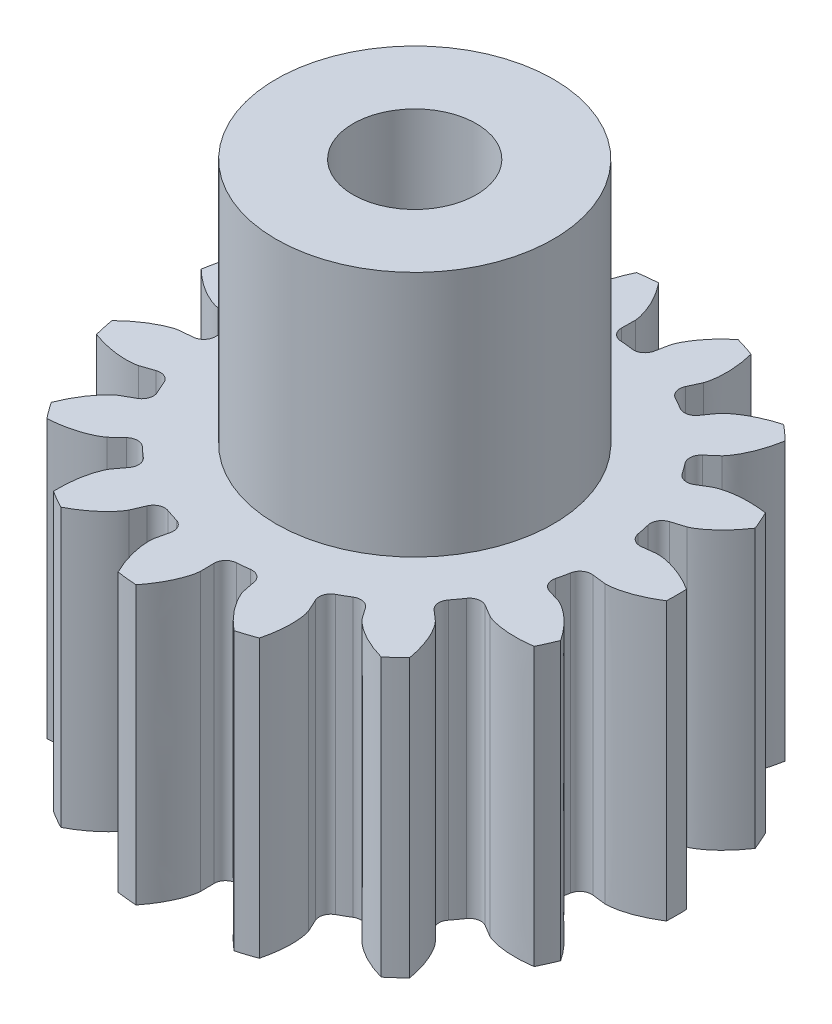
SolidWorks part; units mm, degrees
ref_plane "Front Plane" through (0, 0, 0) normal (0, 0, 1) x (1, 0, 0)
ref_plane "Top Plane" through (0, 0, 0) normal (0, 1, 0) x (1, 0, 0)
ref_plane "Right Plane" through (0, 0, 0) normal (1, 0, 0) x (0, 0, -1)
sketch "Sketch1" plane through (0, 0, 9) normal (0, -1, 0) x (1, 0, 0)
  line L0 (6.5671, -9.7894) -> (7.0134, -9.8423)
  line L1 (7.0134, -8.1577) -> (6.5671, -8.2106)
  line L2 (6.3204, -7.05) -> (6.7496, -6.9168)
  line L3 (6.0645, -5.378) -> (5.6783, -5.6078)
  line L4 (4.9809, -4.6479) -> (5.3188, -4.3516)
  line L5 (4.0669, -3.2245) -> (3.8076, -3.5915)
  line L6 (2.7801, -2.9982) -> (2.9683, -2.5902)
  line L7 (1.3662, -2.0696) -> (1.2786, -2.5104)
  line L8 (0.0986, -2.3864) -> (0.1046, -1.937)
  line L9 (-1.5707, -2.1131) -> (-1.4715, -2.5514)
  line L10 (-2.6, -2.918) -> (-2.7773, -2.5051)
  line L11 (-4.2361, -3.3474) -> (-3.9672, -3.7074)
  line L12 (-4.8489, -4.5013) -> (-5.1789, -4.1962)
  line L13 (-6.169, -5.559) -> (-5.7769, -5.7786)
  line L14 (-6.2595, -6.8625) -> (-6.685, -6.718)
  line L15 (-7.0352, -8.3657) -> (-6.5877, -8.4067)
  line L16 (-6.5877, -9.5933) -> (-7.0352, -9.6343)
  line L17 (-6.685, -11.282) -> (-6.2595, -11.1375)
  line L18 (-5.7769, -12.2214) -> (-6.169, -12.441)
  line L19 (-5.1789, -13.8038) -> (-4.8489, -13.4987)
  line L20 (-3.9672, -14.2926) -> (-4.2361, -14.6526)
  line L21 (-2.7773, -15.4949) -> (-2.6, -15.082)
  line L22 (-1.4715, -15.4486) -> (-1.5707, -15.8869)
  line L23 (0.1046, -16.063) -> (0.0986, -15.6136)
  line L24 (1.2786, -15.4896) -> (1.3662, -15.9304)
  line L25 (2.9683, -15.4098) -> (2.7801, -15.0018)
  line L26 (3.8076, -14.4085) -> (4.0669, -14.7755)
  line L27 (5.3188, -13.6484) -> (4.9809, -13.3521)
  line L28 (5.6783, -12.3922) -> (6.0645, -12.622)
  line L29 (6.7496, -11.0832) -> (6.3204, -10.95)
  arc A0 (6.0668, -10.5021) -> (6.1533, -10.0954) centre (0, -9) ccw
  arc A1 (6.1533, -10.0954) -> (6.5671, -9.7894) centre (6.5224, -10.1617) cw
  arc A2 (8.4936, -9.3269) -> (8.4936, -8.6731) centre (-0.0001, -9) ccw
  arc A3 (6.5671, -8.2106) -> (6.1533, -7.9046) centre (6.5224, -7.8383) cw
  arc A4 (6.1533, -7.9046) -> (6.0668, -7.4979) centre (0, -9) ccw
  arc A5 (6.0668, -7.4979) -> (6.3204, -7.05) centre (6.431, -7.4084) cw
  arc A6 (7.8923, -5.844) -> (7.6263, -5.2467) centre (-0.0001, -9) ccw
  arc A7 (5.6783, -5.6078) -> (5.1758, -5.4966) centre (5.486, -5.2859) cw
  arc A8 (5.1758, -5.4966) -> (4.9314, -5.1602) centre (0, -9) ccw
  arc A9 (4.9314, -5.1602) -> (4.9809, -4.6479) centre (5.2276, -4.9303) cw
  arc A10 (5.9263, -2.9068) -> (5.4404, -2.4692) centre (-0.0001, -9.0001) ccw
  arc A11 (3.8076, -3.5915) -> (3.3033, -3.6943) centre (3.501, -3.3756) cw
  arc A12 (3.3033, -3.6943) -> (2.9432, -3.4864) centre (0, -9) ccw
  arc A13 (2.9432, -3.4864) -> (2.7801, -2.9982) centre (3.1203, -3.1558) cw
  arc A14 (2.9356, -1.0231) -> (2.3137, -0.821) centre (0, -9.0001) ccw
  arc A15 (1.2786, -2.5104) -> (0.8597, -2.8094) centre (0.9107, -2.4379) cw
  arc A16 (0.8597, -2.8094) -> (0.4462, -2.7659) centre (0, -9) ccw
  arc A17 (0.4462, -2.7659) -> (0.0986, -2.3864) centre (0.4735, -2.3919) cw
  arc A18 (-0.5627, -0.5187) -> (-1.213, -0.5871) centre (0, -9.0001) ccw
  arc A19 (-1.4715, -2.5514) -> (-1.7326, -2.9949) centre (-1.8371, -2.6348) cw
  arc A20 (-1.7326, -2.9949) -> (-2.128, -3.1234) centre (0, -9) ccw
  arc A21 (-2.128, -3.1234) -> (-2.6, -2.918) centre (-2.2551, -2.7706) cw
  arc A22 (-3.9637, -1.4808) -> (-4.53, -1.8078) centre (0, -9.0001) ccw
  arc A23 (-3.9672, -3.7074) -> (-4.0252, -4.2188) centre (-4.2672, -3.9323) cw
  arc A24 (-4.0252, -4.2188) -> (-4.3343, -4.497) centre (0, -9) ccw
  arc A25 (-4.3343, -4.497) -> (-4.8489, -4.5013) centre (-4.5939, -4.2264) cw
  arc A26 (-6.6793, -3.7431) -> (-7.0637, -4.2721) centre (0.0001, -9) ccw
  arc A27 (-5.7769, -5.7786) -> (-5.6219, -6.2694) centre (-5.9595, -6.1061) cw
  arc A28 (-5.6219, -6.2694) -> (-5.7911, -6.6492) centre (0, -9) ccw
  arc A29 (-5.7911, -6.6492) -> (-6.2595, -6.8625) centre (-6.1383, -6.5076) cw
  arc A30 (-8.2401, -6.9143) -> (-8.376, -7.5539) centre (0.0001, -9) ccw
  arc A31 (-6.5877, -8.4067) -> (-6.2465, -8.7921) centre (-6.6214, -8.7802) cw
  arc A32 (-6.2465, -8.7921) -> (-6.2465, -9.2079) centre (0, -9) ccw
  arc A33 (-6.2465, -9.2079) -> (-6.5877, -9.5933) centre (-6.6214, -9.2198) cw
  arc A34 (-8.376, -10.4461) -> (-8.2401, -11.0857) centre (0.0001, -9) ccw
  arc A35 (-6.2595, -11.1375) -> (-5.7911, -11.3508) centre (-6.1383, -11.4924) cw
  arc A36 (-5.7911, -11.3508) -> (-5.6219, -11.7306) centre (0, -9) ccw
  arc A37 (-5.6219, -11.7306) -> (-5.7769, -12.2214) centre (-5.9595, -11.8939) cw
  arc A38 (-7.0637, -13.7279) -> (-6.6793, -14.2569) centre (0.0001, -9) ccw
  arc A39 (-4.8489, -13.4987) -> (-4.3343, -13.503) centre (-4.5939, -13.7736) cw
  arc A40 (-4.3343, -13.503) -> (-4.0252, -13.7812) centre (0, -9) ccw
  arc A41 (-4.0252, -13.7812) -> (-3.9672, -14.2926) centre (-4.2672, -14.0677) cw
  arc A42 (-4.53, -16.1922) -> (-3.9637, -16.5192) centre (0, -8.9999) ccw
  arc A43 (-2.6, -15.082) -> (-2.128, -14.8766) centre (-2.2551, -15.2294) cw
  arc A44 (-2.128, -14.8766) -> (-1.7326, -15.0051) centre (0, -9) ccw
  arc A45 (-1.7326, -15.0051) -> (-1.4715, -15.4486) centre (-1.8371, -15.3652) cw
  arc A46 (-1.213, -17.4129) -> (-0.5627, -17.4813) centre (0, -8.9999) ccw
  arc A47 (0.0986, -15.6136) -> (0.4462, -15.2341) centre (0.4735, -15.6081) cw
  arc A48 (0.4462, -15.2341) -> (0.8597, -15.1906) centre (0, -9) ccw
  arc A49 (0.8597, -15.1906) -> (1.2786, -15.4896) centre (0.9107, -15.5621) cw
  arc A50 (2.3137, -17.179) -> (2.9356, -16.9769) centre (0, -8.9999) ccw
  arc A51 (2.7801, -15.0018) -> (2.9432, -14.5136) centre (3.1203, -14.8442) cw
  arc A52 (2.9432, -14.5136) -> (3.3033, -14.3057) centre (0, -9) ccw
  arc A53 (3.3033, -14.3057) -> (3.8076, -14.4085) centre (3.501, -14.6244) cw
  arc A54 (5.4404, -15.5308) -> (5.9263, -15.0932) centre (-0.0001, -8.9999) ccw
  arc A55 (4.9809, -13.3521) -> (4.9314, -12.8398) centre (5.2276, -13.0697) cw
  arc A56 (4.9314, -12.8398) -> (5.1758, -12.5034) centre (0, -9) ccw
  arc A57 (5.1758, -12.5034) -> (5.6783, -12.3922) centre (5.486, -12.7141) cw
  arc A58 (7.6263, -12.7533) -> (7.8923, -12.156) centre (-0.0001, -9) ccw
  arc A59 (6.3204, -10.95) -> (6.0668, -10.5021) centre (6.431, -10.5916) cw
  spline S0 degree 3 poles (7.0134, -9.8423) (7.1365, -9.8462) (7.2601, -9.8267) (7.3807, -9.8012) (7.5494, -9.7655) (7.7147, -9.712) (7.8746, -9.6473) (8.0899, -9.5601) (8.2972, -9.4511) (8.4936, -9.3269) knots 0 0 0 0 0.00037 0.00037 0.00037 0.000887 0.000887 0.000887 0.001584 0.001584 0.001584 0.001584
  spline S1 degree 3 poles (8.4936, -8.6731) (8.3065, -8.5548) (8.1096, -8.4503) (7.9052, -8.3653) (7.7659, -8.3073) (7.6225, -8.258) (7.4762, -8.221) (7.4011, -8.202) (7.325, -8.1862) (7.2484, -8.1749) (7.1707, -8.1633) (7.0919, -8.1553) (7.0134, -8.1577) knots 0 0 0 0 0.000664 0.000664 0.000664 0.001116 0.001116 0.001116 0.001348 0.001348 0.001348 0.001583 0.001583 0.001583 0.001583
  spline S2 degree 3 poles (6.7496, -6.9168) (6.8637, -6.8703) (6.9687, -6.8023) (7.0685, -6.73) (7.208, -6.6287) (7.3374, -6.5126) (7.457, -6.3885) (7.6183, -6.2212) (7.7633, -6.0373) (7.8923, -5.844) knots 0 0 0 0 0.00037 0.00037 0.00037 0.000887 0.000887 0.000887 0.001584 0.001584 0.001584 0.001584
  spline S3 degree 3 poles (7.6263, -5.2467) (7.4073, -5.2147) (7.1849, -5.1994) (6.9636, -5.2048) (6.8128, -5.2085) (6.6617, -5.2218) (6.513, -5.2475) (6.4366, -5.2607) (6.3608, -5.2772) (6.2862, -5.298) (6.2105, -5.3191) (6.1352, -5.3437) (6.0645, -5.378) knots 0 0 0 0 0.000664 0.000664 0.000664 0.001116 0.001116 0.001116 0.001348 0.001348 0.001348 0.001583 0.001583 0.001583 0.001583
  spline S4 degree 3 poles (5.3188, -4.3516) (5.4041, -4.2627) (5.4724, -4.1579) (5.534, -4.0512) (5.6204, -3.9019) (5.6913, -3.7433) (5.7501, -3.5812) (5.8294, -3.3628) (5.8871, -3.1358) (5.9263, -2.9068) knots 0 0 0 0 0.00037 0.00037 0.00037 0.000887 0.000887 0.000887 0.001584 0.001584 0.001584 0.001584
  spline S5 degree 3 poles (5.4404, -2.4692) (5.2273, -2.5292) (5.0179, -2.6056) (4.8179, -2.7006) (4.6816, -2.7653) (4.549, -2.8389) (4.4236, -2.9229) (4.3593, -2.966) (4.2967, -3.0119) (4.237, -3.0612) (4.1764, -3.1113) (4.1176, -3.1644) (4.0669, -3.2245) knots 0 0 0 0 0.000664 0.000664 0.000664 0.001116 0.001116 0.001116 0.001348 0.001348 0.001348 0.001583 0.001583 0.001583 0.001583
  spline S6 degree 3 poles (2.9683, -2.5902) (3.01, -2.4743) (3.0298, -2.3507) (3.0427, -2.2282) (3.0609, -2.0567) (3.0612, -1.8829) (3.049, -1.7109) (3.0326, -1.4791) (2.993, -1.2483) (2.9356, -1.0231) knots 0 0 0 0 0.00037 0.00037 0.00037 0.000887 0.000887 0.000887 0.001584 0.001584 0.001584 0.001584
  spline S7 degree 3 poles (2.3137, -0.821) (2.1435, -0.9625) (1.9832, -1.1175) (1.8392, -1.2855) (1.741, -1.4001) (1.6498, -1.5213) (1.5694, -1.649) (1.5281, -1.7146) (1.4896, -1.782) (1.4551, -1.8513) (1.4202, -1.9217) (1.3881, -1.9942) (1.3662, -2.0696) knots 0 0 0 0 0.000664 0.000664 0.000664 0.001116 0.001116 0.001116 0.001348 0.001348 0.001348 0.001583 0.001583 0.001583 0.001583
  spline S8 degree 3 poles (0.1046, -1.937) (0.0956, -1.8141) (0.0633, -1.6932) (0.0253, -1.576) (-0.0278, -1.412) (-0.0983, -1.2531) (-0.1794, -1.1009) (-0.2886, -0.8959) (-0.4187, -0.7011) (-0.5627, -0.5187) knots 0 0 0 0 0.00037 0.00037 0.00037 0.000887 0.000887 0.000887 0.001584 0.001584 0.001584 0.001584
  spline S9 degree 3 poles (-1.213, -0.5871) (-1.311, -0.7855) (-1.3943, -0.9923) (-1.4576, -1.2044) (-1.5007, -1.349) (-1.5347, -1.4969) (-1.5562, -1.6462) (-1.5672, -1.7229) (-1.575, -1.8001) (-1.5783, -1.8775) (-1.5816, -1.956) (-1.5814, -2.0353) (-1.5707, -2.1131) knots 0 0 0 0 0.000664 0.000664 0.000664 0.001116 0.001116 0.001116 0.001348 0.001348 0.001348 0.001583 0.001583 0.001583 0.001583
  spline S10 degree 3 poles (-2.7773, -2.5051) (-2.8355, -2.3965) (-2.9141, -2.2992) (-2.9965, -2.2076) (-3.1118, -2.0793) (-3.2407, -1.9628) (-3.3767, -1.8568) (-3.5599, -1.7139) (-3.758, -1.5889) (-3.9637, -1.4808) knots 0 0 0 0 0.00037 0.00037 0.00037 0.000887 0.000887 0.000887 0.001584 0.001584 0.001584 0.001584
  spline S11 degree 3 poles (-4.53, -1.8078) (-4.5388, -2.0289) (-4.5308, -2.2517) (-4.5023, -2.4712) (-4.4828, -2.6209) (-4.4538, -2.7698) (-4.4127, -2.915) (-4.3916, -2.9895) (-4.3673, -3.0632) (-4.3388, -3.1352) (-4.3099, -3.2083) (-4.2775, -3.2806) (-4.2361, -3.3474) knots 0 0 0 0 0.000664 0.000664 0.000664 0.001116 0.001116 0.001116 0.001348 0.001348 0.001348 0.001583 0.001583 0.001583 0.001583
  spline S12 degree 3 poles (-5.1789, -4.1962) (-5.2762, -4.1207) (-5.3876, -4.0637) (-5.5001, -4.0136) (-5.6576, -3.9433) (-5.8228, -3.8893) (-5.9902, -3.8478) (-6.2157, -3.7918) (-6.4475, -3.7581) (-6.6793, -3.7431) knots 0 0 0 0 0.00037 0.00037 0.00037 0.000887 0.000887 0.000887 0.001584 0.001584 0.001584 0.001584
  spline S13 degree 3 poles (-7.0637, -4.2721) (-6.9818, -4.4777) (-6.8839, -4.678) (-6.7685, -4.8669) (-6.6899, -4.9957) (-6.6028, -5.1199) (-6.5062, -5.2358) (-6.4566, -5.2953) (-6.4044, -5.3528) (-6.3491, -5.407) (-6.293, -5.462) (-6.234, -5.5149) (-6.169, -5.559) knots 0 0 0 0 0.000664 0.000664 0.000664 0.001116 0.001116 0.001116 0.001348 0.001348 0.001348 0.001583 0.001583 0.001583 0.001583
  spline S14 degree 3 poles (-6.685, -6.718) (-6.8046, -6.6886) (-6.9296, -6.6819) (-7.0528, -6.6818) (-7.2252, -6.6817) (-7.3981, -6.6995) (-7.5679, -6.7296) (-7.7967, -6.7702) (-8.0221, -6.8337) (-8.2401, -6.9143) knots 0 0 0 0 0.00037 0.00037 0.00037 0.000887 0.000887 0.000887 0.001584 0.001584 0.001584 0.001584
  spline S15 degree 3 poles (-8.376, -7.5539) (-8.2176, -7.7084) (-8.0467, -7.8516) (-7.8644, -7.9773) (-7.7402, -8.0629) (-7.6102, -8.141) (-7.4748, -8.2076) (-7.4053, -8.2418) (-7.3342, -8.273) (-7.2616, -8.3001) (-7.188, -8.3275) (-7.1126, -8.3518) (-7.0352, -8.3657) knots 0 0 0 0 0.000664 0.000664 0.000664 0.001116 0.001116 0.001116 0.001348 0.001348 0.001348 0.001583 0.001583 0.001583 0.001583
  spline S16 degree 3 poles (-7.0352, -9.6343) (-7.1565, -9.6561) (-7.2734, -9.7008) (-7.386, -9.7508) (-7.5435, -9.8209) (-7.6942, -9.9075) (-7.8371, -10.0041) (-8.0296, -10.1341) (-8.2097, -10.2839) (-8.376, -10.4461) knots 0 0 0 0 0.00037 0.00037 0.00037 0.000887 0.000887 0.000887 0.001584 0.001584 0.001584 0.001584
  spline S17 degree 3 poles (-8.2401, -11.0857) (-8.0324, -11.1625) (-7.8181, -11.2237) (-7.6005, -11.2644) (-7.4522, -11.2922) (-7.3016, -11.3106) (-7.1508, -11.3164) (-7.0734, -11.3193) (-6.9958, -11.3189) (-6.9185, -11.3141) (-6.8401, -11.3093) (-6.7613, -11.3008) (-6.685, -11.282) knots 0 0 0 0 0.000664 0.000664 0.000664 0.001116 0.001116 0.001116 0.001348 0.001348 0.001348 0.001583 0.001583 0.001583 0.001583
  spline S18 degree 3 poles (-6.169, -12.441) (-6.2709, -12.5102) (-6.3595, -12.5986) (-6.442, -12.6901) (-6.5575, -12.8181) (-6.6599, -12.9586) (-6.7511, -13.1049) (-6.8741, -13.302) (-6.9777, -13.5121) (-7.0637, -13.7279) knots 0 0 0 0 0.00037 0.00037 0.00037 0.000887 0.000887 0.000887 0.001584 0.001584 0.001584 0.001584
  spline S19 degree 3 poles (-6.6793, -14.2569) (-6.4584, -14.2426) (-6.2377, -14.2114) (-6.0224, -14.1601) (-5.8756, -14.1251) (-5.7306, -14.0807) (-5.5905, -14.0246) (-5.5186, -13.9958) (-5.4478, -13.9639) (-5.3791, -13.9281) (-5.3095, -13.8917) (-5.2409, -13.8519) (-5.1789, -13.8038) knots 0 0 0 0 0.000664 0.000664 0.000664 0.001116 0.001116 0.001116 0.001348 0.001348 0.001348 0.001583 0.001583 0.001583 0.001583
  spline S20 degree 3 poles (-4.2361, -14.6526) (-4.301, -14.7573) (-4.3461, -14.8741) (-4.3842, -14.9912) (-4.4376, -15.1552) (-4.474, -15.3251) (-4.4979, -15.4959) (-4.53, -15.726) (-4.5392, -15.9601) (-4.53, -16.1922) knots 0 0 0 0 0.00037 0.00037 0.00037 0.000887 0.000887 0.000887 0.001584 0.001584 0.001584 0.001584
  spline S21 degree 3 poles (-3.9637, -16.5192) (-3.7677, -16.4162) (-3.5788, -16.2979) (-3.4029, -16.1635) (-3.2831, -16.0718) (-3.1686, -15.9722) (-3.0635, -15.864) (-3.0095, -15.8085) (-2.9578, -15.7506) (-2.9096, -15.6899) (-2.8608, -15.6284) (-2.8144, -15.5641) (-2.7773, -15.4949) knots 0 0 0 0 0.000664 0.000664 0.000664 0.001116 0.001116 0.001116 0.001348 0.001348 0.001348 0.001583 0.001583 0.001583 0.001583
  spline S22 degree 3 poles (-1.5707, -15.8869) (-1.5875, -16.009) (-1.5811, -16.134) (-1.5683, -16.2565) (-1.5504, -16.428) (-1.5145, -16.598) (-1.4669, -16.7638) (-1.4026, -16.9871) (-1.3159, -17.2046) (-1.213, -17.4129) knots 0 0 0 0 0.00037 0.00037 0.00037 0.000887 0.000887 0.000887 0.001584 0.001584 0.001584 0.001584
  spline S23 degree 3 poles (-0.5627, -17.4813) (-0.4255, -17.3075) (-0.301, -17.1226) (-0.1951, -16.9283) (-0.1229, -16.7958) (-0.0588, -16.6583) (-0.0067, -16.5166) (0.02, -16.4439) (0.0436, -16.37) (0.0629, -16.295) (0.0825, -16.2189) (0.0988, -16.1413) (0.1046, -16.063) knots 0 0 0 0 0.000664 0.000664 0.000664 0.001116 0.001116 0.001116 0.001348 0.001348 0.001348 0.001583 0.001583 0.001583 0.001583
  spline S24 degree 3 poles (1.3662, -15.9304) (1.4006, -16.0487) (1.4572, -16.1603) (1.5188, -16.267) (1.6049, -16.4164) (1.7068, -16.5572) (1.8177, -16.6892) (1.9673, -16.867) (2.135, -17.0305) (2.3137, -17.179) knots 0 0 0 0 0.00037 0.00037 0.00037 0.000887 0.000887 0.000887 0.001584 0.001584 0.001584 0.001584
  spline S25 degree 3 poles (2.9356, -16.9769) (2.9902, -16.7624) (3.0288, -16.5428) (3.0465, -16.3222) (3.0586, -16.1718) (3.0612, -16.0201) (3.0511, -15.8695) (3.046, -15.7922) (3.0375, -15.7151) (3.0246, -15.6387) (3.0116, -15.5612) (2.9949, -15.4838) (2.9683, -15.4098) knots 0 0 0 0 0.000664 0.000664 0.000664 0.001116 0.001116 0.001116 0.001348 0.001348 0.001348 0.001583 0.001583 0.001583 0.001583
  spline S26 degree 3 poles (4.0669, -14.7755) (4.1464, -14.8696) (4.2436, -14.9485) (4.3432, -15.021) (4.4827, -15.1225) (4.633, -15.2096) (4.7881, -15.2851) (4.997, -15.3867) (5.2167, -15.4678) (5.4404, -15.5308) knots 0 0 0 0 0.00037 0.00037 0.00037 0.000887 0.000887 0.000887 0.001584 0.001584 0.001584 0.001584
  spline S27 degree 3 poles (5.9263, -15.0932) (5.889, -14.8751) (5.8349, -14.6588) (5.7613, -14.45) (5.7112, -14.3077) (5.6518, -14.1681) (5.5814, -14.0346) (5.5453, -13.9661) (5.5062, -13.8991) (5.4633, -13.8345) (5.4199, -13.7691) (5.3732, -13.7051) (5.3188, -13.6484) knots 0 0 0 0 0.000664 0.000664 0.000664 0.001116 0.001116 0.001116 0.001348 0.001348 0.001348 0.001583 0.001583 0.001583 0.001583
  spline S28 degree 3 poles (6.0645, -12.622) (6.1754, -12.6757) (6.2962, -12.7082) (6.4167, -12.7339) (6.5853, -12.7699) (6.7581, -12.7883) (6.9305, -12.7942) (7.1627, -12.8021) (7.3964, -12.7868) (7.6263, -12.7533) knots 0 0 0 0 0.00037 0.00037 0.00037 0.000887 0.000887 0.000887 0.001584 0.001584 0.001584 0.001584
  spline S29 degree 3 poles (7.8923, -12.156) (7.7694, -11.9719) (7.632, -11.7963) (7.4799, -11.6355) (7.3763, -11.5259) (7.2653, -11.4225) (7.1467, -11.3292) (7.0858, -11.2813) (7.0228, -11.236) (6.9574, -11.1944) (6.8911, -11.1523) (6.8224, -11.1128) (6.7496, -11.0832) knots 0 0 0 0 0.000664 0.000664 0.000664 0.001116 0.001116 0.001116 0.001348 0.001348 0.001348 0.001583 0.001583 0.001583 0.001583
extrude "Boss-Extrude1" add sketch "Sketch1" against normal blind 4.5 and the other way blind 4.5
sketch "Sketch2" plane through (0, 4.5, 0) normal (0, 1, 0) x (1, 0, 0)
  circle A0 centre (0, 0) radius 4.5
  dimension "D1" = 9
extrude "Boss-Extrude2" add sketch "Sketch2" along normal blind 8
sketch "Sketch3" plane through (0, 12.5, 0) normal (0, 1, 0) x (1, 0, 0)
  circle A0 centre (0, 0) radius 2
  dimension "D1" = 4
extrude "Cut-Extrude1" cut sketch "Sketch3" against normal up to next
